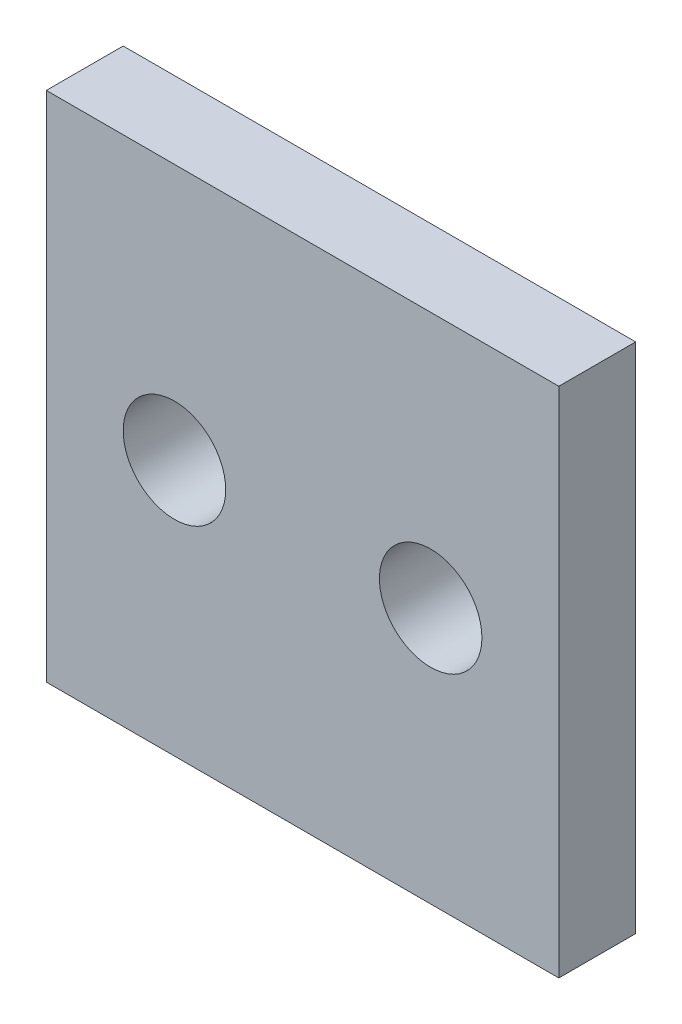
SolidWorks part; units mm, degrees
ref_plane "Alzado" through (0, 0, 0) normal (0, 0, 1) x (1, 0, 0)
ref_plane "Planta" through (0, 0, 0) normal (0, 1, 0) x (1, 0, 0)
ref_plane "Vista lateral" through (0, 0, 0) normal (1, 0, 0) x (0, 0, -1)
sketch "Croquis1" plane through (0, 0, 0) normal (0, 0, 1) x (1, 0, 0)
  line L1 (-5, 5) -> (5, 5)
  line L2 (-5, 5) -> (-5, -5)
  line L3 (-5, -5) -> (5, -5)
  line L4 (5, 5) -> (5, -5)
  line L5 (-5, 5) -> (5, -5) construction
  line L6 (-5, -5) -> (5, 5) construction
  circle A0 centre (-2.5, 0) radius 1
  circle A1 centre (2.5, 0) radius 1
  point P0 (0, 0)
  point P11 (0, 0)
  point P12 (0, 0)
  dimension "D1" = 10
  dimension "D2" = 10
  dimension "D3" = 2
  dimension "D4" = 2.5
  dimension "D5" = 2.5
extrude "Saliente-Extruir6" add sketch "Croquis1" along normal blind 1.5
sketch "Croquis8" plane through (0, 0, 0) normal (1, 0, 0) x (0, 0, -1)
  line L0 (0, -5) -> (0, 5) construction
  line L1 (0, 3) -> (0, 1.5)
  line L2 (0, -1.5) -> (0, -3)
  arc A0 (0, -1.5) -> (0, 1.5) centre (0, 0) ccw
  arc A1 (0, -3) -> (0, 3) centre (0, 0) ccw
  dimension "D1" = 3
  dimension "D2" = 1.5
extrude "Saliente-Extruir7" add sketch "Croquis8" along normal blind 0.75 and the other way blind 0.75
